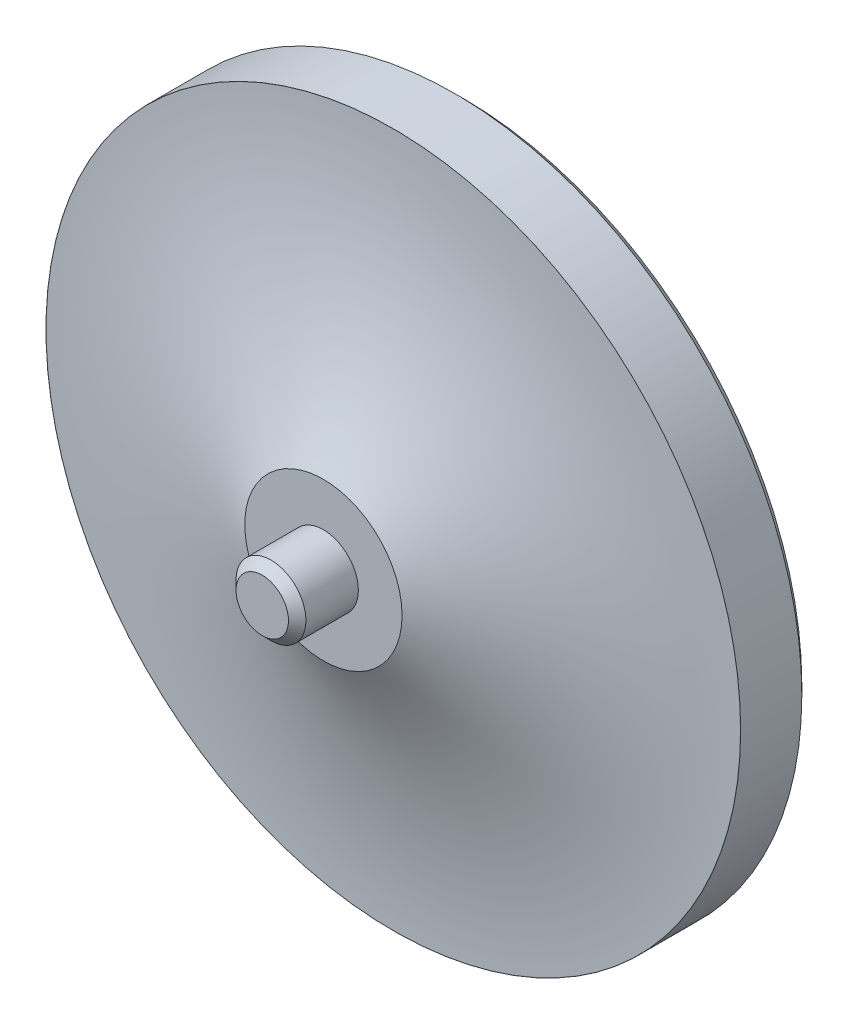
SolidWorks part; units mm, degrees
ref_plane "Front Plane" through (0, 0, 0) normal (0, 0, 1) x (1, 0, 0)
ref_plane "Top Plane" through (0, 0, 0) normal (0, 1, 0) x (1, 0, 0)
ref_plane "Right Plane" through (0, 0, 0) normal (1, 0, 0) x (0, 0, -1)
sketch "Sketch1" plane through (0, 0, 0) normal (0, 0, 1) x (1, 0, 0)
  circle A0 centre (0, 0) radius 39.75
  dimension "D1" = 79.5
extrude "Boss-Extrude1" add sketch "Sketch1" along normal blind 8
chamfer "Chamfer1" distance 1 angle 45 1 edges at (39.75, 0, 0)
sketch "Sketch2" plane through (0, 0, 8) normal (0, 0, 1) x (1, 0, 0)
  circle A0 centre (0, 0) radius 4
  circle A2 centre (0, 0) radius 9
  dimension "D1" = 8
  dimension "D2" = 5
extrude "Boss-Extrude2" add sketch "Sketch2" along normal blind 8 contours A0 | A2 A0 region at (0, 0, 8) region at (-8.7454, 0, 8)
extrude "Boss-Extrude3" add sketch "Sketch2<3>" along normal blind 7 from surface contours A0 region at (0, 0, 8) starting at face at (9, 0, 16)
sketch "Sketch2<3>" plane through (0, 0, 8) normal (0, 0, 1) x (1, 0, 0) same geometry as "Sketch2"
fillet "Fillet1" radius 63 1 edges at (9, 0, 8)
chamfer "Chamfer2" distance 1 angle 45 1 edges at (4, 0, 23)
